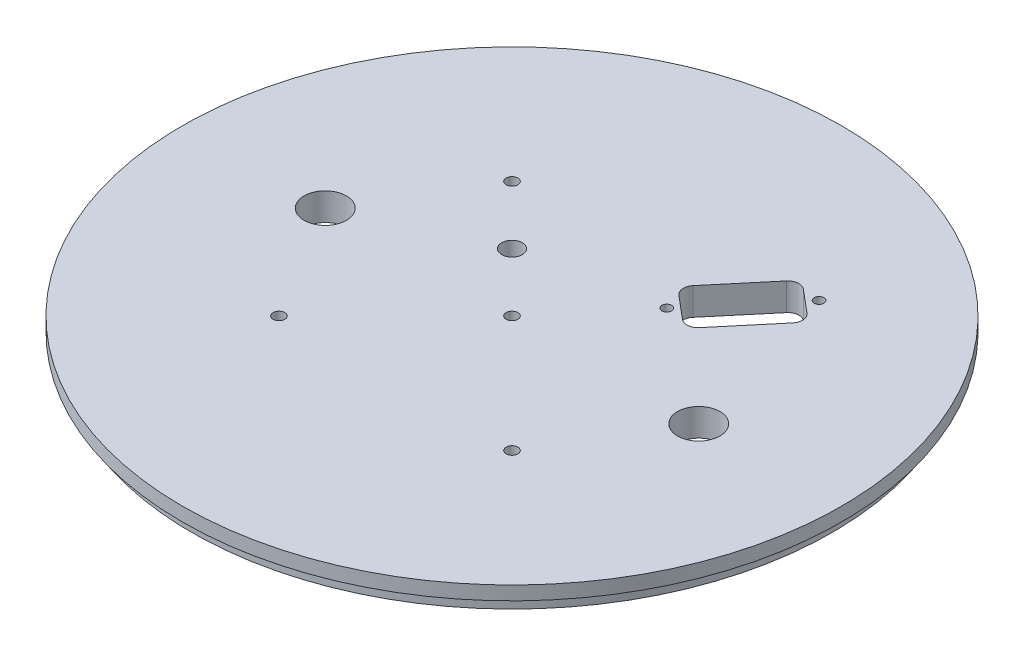
SolidWorks part; units mm, degrees
material "6061-T6 (SS)"
ref_plane "Front Plane" through (0, 0, 0) normal (0, 0, 1) x (1, 0, 0)
ref_plane "Top Plane" through (0, 0, 0) normal (0, 1, 0) x (1, 0, 0)
ref_plane "Right Plane" through (0, 0, 0) normal (1, 0, 0) x (0, 0, -1)
sketch "Sketch1" plane through (0, 0, 0) normal (0, 1, 0) x (1, 0, 0)
  line L0 (0, -76.2) -> (0, 76.2) construction
  line L1 (-76.2, 0) -> (76.2, 0) construction
  line L2 (-26.9408, 26.9408) -> (0, 0) construction
  line L3 (0, 56.7387) -> (0, 29.6936) construction
  line L4 (3.6407, 56.7387) -> (3.6407, 29.6936) construction
  line L5 (-3.6407, 56.7387) -> (-3.6407, 29.6936) construction
  line L6 (0, -56.7387) -> (0, -29.6936) construction
  line L7 (3.6407, -56.7387) -> (3.6407, -29.6936) construction
  line L8 (-3.6407, -56.7387) -> (-3.6407, -29.6936) construction
  line L9 (-53.8815, -53.8815) -> (54.3236, 54.3236) construction
  line L10 (-26.9408, -26.9408) -> (0, 0) construction
  circle A0 centre (0, 0) radius 76.2
  circle A1 centre (0, 0) radius 3.175 construction
  circle A2 centre (43.18, 0) radius 4.9022
  circle A3 centre (-43.18, 0) radius 4.9022
  circle A4 centre (-26.9408, 26.9408) radius 1.3589
  arc A6 (3.6407, 56.7387) -> (-3.6407, 56.7387) centre (0, 56.7387) ccw construction
  arc A7 (-3.6407, 29.6936) -> (3.6407, 29.6936) centre (0, 29.6936) ccw construction
  arc A8 (3.6407, -56.7387) -> (-3.6407, -56.7387) centre (0, -56.7387) cw construction
  arc A9 (-3.6407, -29.6936) -> (3.6407, -29.6936) centre (0, -29.6936) cw construction
  circle A10 centre (26.9408, -26.9408) radius 1.3589
  circle A11 centre (-13.4704, 13.4704) radius 2.3813
  circle A13 centre (-26.9408, -26.9408) radius 1.3589
  circle A14 centre (0, 0) radius 38.1 construction
  circle A15 centre (0, 0) radius 1.3589
  point P16 (0, 43.2162)
  point P19 (0, 0)
  point P26 (0, -43.2162)
  dimension "D1" = 152.4
  dimension "D2" = 6.35
  dimension "D3" = 9.8044
  dimension "D5" = 2.7178
  dimension "D8" = 4.7625
  dimension "D10" = 2.7178
  dimension "D12" = 2.7178
  dimension "D6" = 38.1
  dimension "D7" = 45
  dimension "D4" = 45
  dimension "D9" = 43.18
  dimension "D11" = 38.1
extrude "Boss-Extrude1" add sketch "Sketch1" along normal blind 6.35
sketch "Sketch2" plane through (0, 0, 0) normal (0, -1, 0) x (1, 0, 0)
  circle A0 centre (0, 0) radius 76.2
  circle A1 centre (0, 0) radius 74.041
  dimension "D1" = 152.4
  dimension "D2" = 148.082
extrude "Cut-Extrude1" cut sketch "Sketch2" against normal blind 3.175
sketch "Sketch3" plane through (0, 6.35, 0) normal (0, 1, 0) x (1, 0, 0)
  line L0 (0, 76.2) -> (0, -76.2) construction
  line L1 (-76.2, 0) -> (76.2, 0) construction
  line L2 (0, 34.798) -> (0, 13.97) construction
  line L3 (3.2385, 34.798) -> (3.2385, 13.97)
  line L4 (-3.2385, 34.798) -> (-3.2385, 13.97)
  line L5 (0, -34.798) -> (0, -13.97) construction
  line L6 (3.2385, -34.798) -> (3.2385, -13.97)
  line L7 (-3.2385, -34.798) -> (-3.2385, -13.97)
  circle A0 centre (0, 0) radius 76.2 construction
  arc A1 (3.2385, 34.798) -> (-3.2385, 34.798) centre (0, 34.798) ccw
  arc A2 (-3.2385, 13.97) -> (3.2385, 13.97) centre (0, 13.97) ccw
  arc A3 (3.2385, -34.798) -> (-3.2385, -34.798) centre (0, -34.798) cw
  arc A4 (-3.2385, -13.97) -> (3.2385, -13.97) centre (0, -13.97) cw
  point P7 (0, 13.97)
  point P8 (0, 34.798)
  point P12 (0, 24.384)
  point P20 (0, -24.384)
  point P25 (0, -34.798)
  point P26 (0, -13.97)
  dimension "D1" = 13.97
  dimension "D2" = 20.828
  dimension "D3" = 6.477
extrude "Cut-Extrude2" cut sketch "Sketch3" against normal blind 3.556 from offset 3.175 offset against normal yes
hole_wizard "Tap Drill for #4-40 Tap1" positions "Sketch5" profile "Sketch6" hole size "#4-40" standard "ANSI Inch" end condition through all
sketch "Sketch5" plane through (0, 6.35, 0) normal (0, 1, 0) x (1, 0, 0)
  line L0 (0, 0) -> (53.6567, 63.9455) construction
  line L2 (0, 0) -> (43.18, 0) construction
  point P0 (16.3268, 19.4575)
  point P2 (32.3965, 38.6086)
  dimension "D1" = 50
  dimension "D2" = 25
  dimension "D3" = 25.4
sketch "Sketch6" plane through (16.3268, 6.35, -19.4575) normal (1, 0, 0) x (0, 0, 1)
  line L0 (0, 0) -> (0, 6.35)
  line L1 (0, 6.35) -> (1.1303, 6.35)
  line L2 (1.1303, 6.35) -> (1.1303, 0)
  line L5 (1.1303, 0) -> (0, 0)
  line L11 (0, -6.35) -> (0, 107.95) construction
  dimension "Thru Hole Dia." = 2.2606
  dimension "Thru Hole Depth" = 6.35
sketch "Sketch4" plane through (0, 6.35, 0) normal (0, 1, 0) x (1, 0, 0)
  line L0 (15.1695, 23.4128) -> (20.423, 19.0046)
  line L1 (14.8564, 26.9913) -> (24.7219, 38.7485)
  line L2 (24.0014, 19.3177) -> (33.8669, 31.0749)
  line L3 (28.3003, 39.0616) -> (33.5538, 34.6533)
  line L4 (0, 0) -> (32.3965, 38.6086) construction
  circle A1 centre (16.3268, 19.4575) radius 1.1303 construction
  arc A2 (24.7219, 38.7485) -> (28.3003, 39.0616) centre (26.6676, 37.1158) cw
  arc A3 (33.8669, 31.0749) -> (33.5538, 34.6533) centre (31.9212, 32.7076) ccw
  arc A4 (20.423, 19.0046) -> (24.0014, 19.3177) centre (22.0557, 20.9503) ccw
  arc A5 (14.8564, 26.9913) -> (15.1695, 23.4128) centre (16.8021, 25.3586) ccw
  point P11 (17.7962, 21.2087)
  dimension "D4" = 2.54
  dimension "D1" = 2.286
  dimension "D2" = 2.286
  dimension "D3" = 11.938
extrude "Cut-Extrude3" cut sketch "Sketch4" against normal through all
equation "\"leadDist\"=1.5"
equation "\"Lead_Screw_Dist\" = 3.4in"
equation "\"D9@Sketch1\"=\"Lead_Screw_Dist\"/2"
equation "\"Lead_Screw_Diam\" = 0.386in"
equation "\"D3@Sketch1\"=\"Lead_Screw_Diam\""
equation "\"Bodytube_OD\" = 6.17in"
equation "\"Bodytube_ID\" = 5.998in"
equation "\"Motor_OD\" = 4in"
equation "\"Fwd_Tube_Length\" = 40in"
equation "\"Mid_Tube_Length\"= 1in"
equation "\"Aft_Section_Length\"= 39in"
equation "\"AB_Coupler_OD_Length\"= 1in"
equation "\"AB_Coupling_Section_Length\"= 0.375in"
equation "\"AB_Coupler_Length\"= \"AB_Coupler_OD_Length\" + \"AB_Coupling_Section_Length\" * 2"
equation "\"Cutout_Angle\" = 80"
equation "\"AB_Paddle_Height\" = 0.375in"
equation "\"AB_Coupler_Num_Screws\"= 4"
equation "\"Num_Cutouts\" = 3"
equation "\"AB_Coupler_OD\"= 6.17in"
equation "\"AB_Coupler_ID\"= 5.75in"
equation "\"AB_Coupler_Surface_Diameter\"= 5.998in"
equation "\"AB_Coupling_Screw_Diameter\"= 0.15748in"
equation "\"AB_Central_Bushing_Length\" = .4724in"
equation "\"Lead_Screw_Length\" = (\"Mid_Coupler_Length\" + 2*0.375in + 2*0.5in)"
equation "\"Paddle_Pin_Offset\" = .25in"
equation "\"Paddle_Pin_Radius\" = 2.25in"
equation "\"SS_Paddle_Pin_Radius\" = 2.25*0.66in"
equation "\"Paddle_Gear_OD\" = 3.2in"
equation "\"Drive_Gear_OD\" = 1.7in"
equation "\"Fwd_BKHD_From_Top\" = 18in"
equation "\"Fin_Thickness\"= .118in"
equation "\"Guiderail_Cutout_Diameter\"= 1.5in"
equation "\"DB9_Hole_Dist\" = 25mm"
equation "\"Airbrakes_Wire_Hole_Dia\" = .25in"
equation "\"Airbrakes_Wire_Hole_Dist\" = 1.1in"
equation "\"Servo_Gear_Offset\" = 0.5in"
equation "\"Mid_Coupler_Length\" = 13in"
equation "\"D2@Sketch5\"=\"DB9_Hole_Dist\""
equation "\"DB9_Relief_Width\" = 0.47in"
equation "\"DB9_Relief_Hole_Offset\" = 0.09in"
equation "\"D1@Sketch4\"=\"DB9_Relief_Hole_Offset\""
equation "\"D2@Sketch4\"=\"DB9_Relief_Hole_Offset\""
equation "\"D3@Sketch4\"=\"DB9_Relief_Width\""
